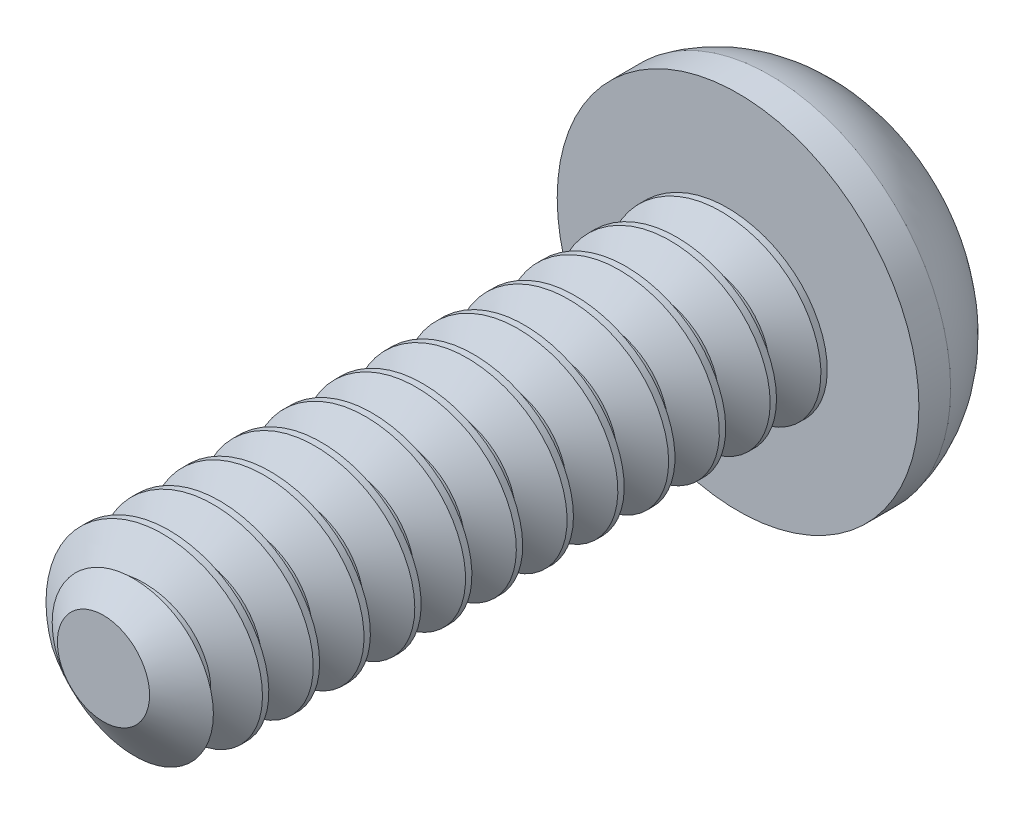
SolidWorks part; units mm, degrees
ref_plane "Front Plane" through (0, 0, 0) normal (0, 0, 1) x (1, 0, 0)
ref_plane "Top Plane" through (0, 0, 0) normal (0, 1, 0) x (1, 0, 0)
ref_plane "Right Plane" through (0, 0, 0) normal (1, 0, 0) x (0, 0, -1)
sketch "Sketch1" plane through (0, 0, 0) normal (0, 0, 1) x (1, 0, 0)
  circle A0 centre (0, 0) radius 1.5
  dimension "OD" = 3
extrude "Extrude1" add sketch "Sketch1" against normal blind 10
sketch "Sketch2" plane through (0, 0, 0) normal (0, 0, 1) x (1, 0, 0)
  circle A0 centre (0, 0) radius 1.5 construction
  circle A1 centre (0, 0) radius 1.5
curve "Helix/Spiral1" pitch 0.8 height 10.8 turns 13.5 parameters "pitch"=0.8
sketch "Sketch3" plane through (0, 0, 0) normal (1, 0, 0) x (0, 0, -1)
  line L0 (-0.7, 1.5) -> (-0.4, 0.9804)
  line L1 (-0.4, 0.9804) -> (-0.3, 0.9804)
  line L2 (-0.3, 0.9804) -> (0, 1.5)
  line L3 (-0.7, 1.5) -> (0, 1.5)
  line L4 (-0.35, 1.5) -> (-0.35, 0.9804) construction
  line L5 (-0.55, 1.2402) -> (-0.15, 1.2402) construction
  line L6 (0, 1.5) -> (0, -1.5) construction
  dimension "D1" = 0.1
  dimension "D2" = 0.4
  dimension "D3" = 60
sweep "Cut-Sweep1" cut profiles "Sketch3" path "Helix/Spiral1"
sketch "Sketch4" plane through (0, 0, 0) normal (1, 0, 0) x (0, 0, -1)
  line L0 (0.5417, 1.5) -> (0, 0.7264)
  line L1 (0, 0.7264) -> (0, 1.5)
  line L2 (0.5417, 1.5) -> (0, 1.5)
  line L3 (-0.7, 1.5) -> (0, 1.5) construction
  line L4 (0, 0) -> (7.0209, 0) construction
  dimension "D1" = 55
  dimension "D2" = 0.254
revolve "Cut-Revolve1" cut sketch "Sketch4" angle 360 about L4
sketch "Sketch5" plane through (0, 0, 0) normal (1, 0, 0) x (0, 0, -1)
  line L0 (10, -1.0703) -> (10, 1.0021) construction
  line L1 (10, 1.627) -> (28.1202, 1.627)
  line L2 (10, 1.627) -> (10, 0)
  line L3 (10, 0) -> (28, 0)
  line L4 (28, 1.2968) -> (28, 0)
  line L5 (28.1202, 1.627) -> (28, 1.2968)
  line L6 (0, 0) -> (9.9695, 0) construction
  point P3 (28, 1.627)
  point P10 (28, 1.627)
  dimension "D1" = 0.3302
  dimension "Thread min" = 28
  dimension "D2" = 0.127
  dimension "D3" = 20
sketch "Sketch6" plane through (0, 0, -10) normal (0, 0, -1) x (-1, 0, 0)
  circle A0 centre (0, 0) radius 2.85
  dimension "head dia" = 5.7
extrude "Extrude2" add sketch "Sketch6" along normal blind 2
sketch "Sketch10" plane through (0, 0, 0) normal (1, 0, 0) x (0, 0, -1)
  line L0 (12, -2.85) -> (12, 2.85) construction
  line L1 (0, 0) -> (15.9584, 0) construction
  line L2 (12, 2.85) -> (10, 2.85) construction
  line L3 (10, 2.85) -> (10, -2.85) construction
  line L4 (10.5, 2.85) -> (10.5, 3.35)
  line L5 (10.5, 3.35) -> (12.5, 3.35)
  line L6 (12.5, 3.35) -> (12.5, 1)
  line L7 (12, 1) -> (12.5, 1)
  arc A0 (12, 1) -> (10.5, 2.85) centre (10.1092, 1) ccw
  dimension "D1" = 2
  dimension "D2" = 0.5
  dimension "D3" = 0.5
revolve "Cut-Revolve2" cut sketch "Sketch10" angle 360 about L1
ref_plane "Plane1" through (0, 0, -12) normal (0, 0, 1) x (1, 0, 0)
sketch "Sketch7" plane through (0, 0, -12) normal (0, 0, -1) x (-1, 0, 0)
  line L1 (0, 1.1547) -> (-1, 0.5774)
  line L2 (-1, 0.5774) -> (-1, -0.5774)
  line L3 (-1, -0.5774) -> (0, -1.1547)
  line L4 (0, -1.1547) -> (1, -0.5774)
  line L5 (1, -0.5774) -> (1, 0.5774)
  line L6 (1, 0.5774) -> (0, 1.1547)
  circle A0 centre (0, 0) radius 1 construction
  dimension "hex dia" = 2
extrude "Cut-Extrude1" cut sketch "Sketch7" against normal blind 1.5
sketch "Sketch8" plane through (0, 0, -12) normal (0, 0, 1) x (1, 0, 0)
  circle A0 centre (0, 0) radius 1.1547
extrude "Cut-Extrude2" cut sketch "Sketch8" along normal through all draft 45
sketch "Sketch9" plane through (0, 0, 0) normal (1, 0, 0) x (0, 0, -1)
  line L0 (0, 1.5) -> (0, -1.5) construction
  line L1 (4.4, 1.5) -> (4.4, -1.5) construction
  dimension "D1" = 4.4
equation "\"D3@Helix/Spiral1\" = \"screw length@Extrude1\"+\"pitch@Helix/Spiral1\""
equation "\"D1@Sketch3\" = \"pitch@Helix/Spiral1\"*.125"
equation "\"D2@Sketch3\" = \"pitch@Helix/Spiral1\"*.5"
equation "\"D1@Cut-Extrude1\" = \"hex dia@Sketch7\"*.75"
equation "\"D1@Sketch9\" = \"pitch@Helix/Spiral1\"*5.5"
equation "\"D1@Sketch10\" = \"hex dia@Sketch7\""
equation "\"D1@Plane1\" = \"head depth@Extrude2\""
